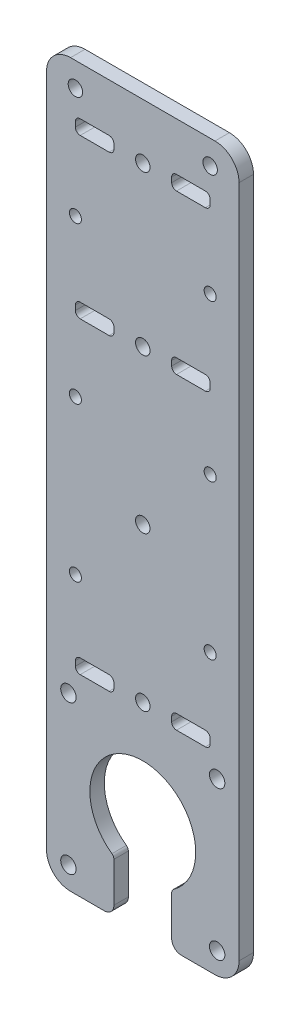
SolidWorks part; units mm, degrees
material "Acrylic (Medium-high impact)"
ref_plane "Front Plane" through (0, 0, 0) normal (0, 0, 1) x (1, 0, 0)
ref_plane "Top Plane" through (0, 0, 0) normal (0, 1, 0) x (1, 0, 0)
ref_plane "Right Plane" through (0, 0, 0) normal (1, 0, 0) x (0, 0, -1)
sketch "Sketch1" plane through (0, 0, 0) normal (0, 0, 1) x (1, 0, 0)
  line L0 (0, 75) -> (0, -75) construction
  line L1 (-20, 75) -> (20, 75)
  line L2 (-20, 75) -> (-20, -75)
  line L3 (-20, -75) -> (20, -75)
  line L4 (20, 75) -> (20, -75)
  line L5 (20, 0) -> (-20, 0) construction
  line L6 (0, -75) -> (0, -55) construction
  line L7 (0, -55) -> (6, -55) construction
  line L8 (6, -55) -> (6, -75) construction
  line L9 (0, -55) -> (-6, -55) construction
  line L10 (-6, -55) -> (-6, -75) construction
  line L11 (0, -55) -> (20, -75) construction
  line L12 (0, -55) -> (15.4503, -70.4503) construction
  line L13 (-6, -75) -> (-6, -64.2195)
  line L14 (6, -75) -> (6, -64.2195)
  line L15 (0, -75) -> (0, -35) construction
  line L16 (-20, -35) -> (20, -35) construction
  line L17 (0, -35) -> (0, -32) construction
  line L18 (-20, -32) -> (20, -32) construction
  circle A0 centre (0, -55) radius 11
  circle A1 centre (15.4503, -70.4503) radius 1.6
  circle A2 centre (-15.4503, -70.4503) radius 1.6
  circle A3 centre (-15.4503, -39.5497) radius 1.6
  circle A4 centre (15.4503, -39.5497) radius 1.6
  point P8 (0, 0)
  point P26 (0, -55)
  dimension "D1" = 4
extrude "Boss-Extrude1" add sketch "Sketch1" along normal blind 3 contours A0 L14 L3 L4 L1 L2 L13 A4 A3 A2 A1 region at (0, 5.617, 0)
fillet "Fillet1" radius 5 4 edges at (-20, -75, 1.5) (20, -75, 1.5) (-20, 75, 1.5) (20, 75, 1.5)
fillet "Fillet2" radius 2 2 edges at (6, -75, 1.5) (-6, -75, 1.5)
fillet "Fillet3" radius 1 2 edges at (6, -64.2195, 1.5) (-6, -64.2195, 1.5)
sketch "Sketch2" plane through (0, 0, 3) normal (0, 0, 1) x (1, 0, 0)
  line L0 (0, -75) -> (0, -35) construction
  line L1 (0, -35) -> (0, -33.5) construction
  line L2 (-20, -33.5) -> (20, -33.5) construction
  line L3 (-20, 70) -> (-20, -70) construction
  line L4 (20, 70) -> (20, -70) construction
  line L5 (-20, -35) -> (20, -35) construction
  line L6 (20, -35) -> (20, -32)
  line L7 (20, -32) -> (-20, -32) construction
  line L8 (-20, -32) -> (-20, -35)
  line L9 (0, 75) -> (0, 65) construction
  line L10 (-15, 75) -> (15, 75) construction
  line L11 (0, 65) -> (0, 62) construction
  line L12 (0, 62) -> (0, 32) construction
  line L13 (0, 32) -> (0, 29) construction
  line L14 (-20, 29) -> (20, 29) construction
  line L15 (20, 29) -> (20, 32) construction
  line L16 (20, 32) -> (-20, 32) construction
  line L17 (-20, 32) -> (-20, 29) construction
  line L18 (-20, 62) -> (20, 62) construction
  line L19 (20, 62) -> (20, 65) construction
  line L20 (-10, 65) -> (-10, -35) construction
  line L21 (-20, 65) -> (-20, 62) construction
  line L22 (-20, 65) -> (0, 65) construction
  line L23 (0, 65) -> (20, 65) construction
  line L24 (10, 65) -> (10, -35) construction
  line L25 (0, -33.5) -> (0, 30.5) construction
  line L26 (-10, 65) -> (-6, 65) construction
  line L27 (-10, 65) -> (-14, 65) construction
  line L28 (10, 65) -> (14, 65) construction
  line L29 (10, 65) -> (6, 65) construction
  line L30 (6, 65) -> (6, -35) construction
  line L31 (14, 65) -> (14, -35) construction
  line L32 (-14, 65) -> (-14, -35) construction
  line L33 (-6, 65) -> (-6, -35) construction
  line L34 (0, 29) -> (0, -32) construction
  line L35 (-14, 65) -> (-6, 65)
  line L36 (-14, 65) -> (-14, 62)
  line L37 (-14, 62) -> (-6, 62)
  line L38 (-6, 65) -> (-6, 62)
  line L39 (6, 65) -> (14, 65)
  line L40 (6, 65) -> (6, 62)
  line L41 (6, 62) -> (14, 62)
  line L42 (14, 65) -> (14, 62)
  line L43 (-14, 32) -> (-6, 32)
  line L44 (-14, 32) -> (-14, 29)
  line L45 (-14, 29) -> (-6, 29)
  line L46 (-6, 32) -> (-6, 29)
  line L47 (6, 32) -> (14, 32)
  line L48 (6, 32) -> (6, 29)
  line L49 (6, 29) -> (14, 29)
  line L50 (14, 32) -> (14, 29)
  line L51 (-14, -32) -> (-6, -32)
  line L52 (-14, -32) -> (-14, -35)
  line L53 (-14, -35) -> (-6, -35)
  line L54 (-6, -32) -> (-6, -35)
  line L55 (6, -32) -> (14, -32)
  line L56 (6, -32) -> (6, -35)
  line L57 (6, -35) -> (14, -35)
  line L58 (14, -32) -> (14, -35)
  circle A0 centre (0, -33.5) radius 1.5
  circle A1 centre (0, 30.5) radius 1.5
  circle A2 centre (0, 63.5) radius 1.5
  circle A3 centre (0, -1.5) radius 1.5
extrude "Cut-Extrude1" cut sketch "Sketch2" against normal blind 3 contours L54 L51 L52 L53 | L58 L55 L56 L57 | A0 | A1 | L50 L47 L48 L49 | L46 L43 L44 L45 | A2 | L38 L35 L36 L37 | L42 L39 L40 L41 | A3 region at (-10, 63.5, 3) region at (10, 63.5, 3) region at (-10, 30.5, 3) region at (10, 30.5, 3) region at (-10, -33.5, 3) region at (10, -33.5, 3) region at (0, -33.5, 3) region at (0, 30.5, 3) region at (0, 63.5, 3) region at (0, -1.5, 3)
fillet "Fillet4" radius 1 24 edges at (-6, 29, 1.5) (-14, 29, 1.5) (-6, 32, 1.5) (14, -35, 1.5) (6, -35, 1.5) (6, -32, 1.5) (14, -32, 1.5) (-6, -35, 1.5) (-14, -35, 1.5) (-14, -32, 1.5) (-6, -32, 1.5) (14, 29, 1.5) (6, 29, 1.5) (6, 32, 1.5) (14, 32, 1.5) (-14, 32, 1.5) (14, 65, 1.5) (14, 62, 1.5) (6, 65, 1.5) (6, 62, 1.5) (-14, 62, 1.5) (-6, 62, 1.5) (-6, 65, 1.5) (-14, 65, 1.5)
sketch "Sketch3" plane through (0, 0, 3) normal (0, 0, 1) x (1, 0, 0)
  line L0 (-14, 30.5) -> (-14, -1.5) construction
  line L1 (14, -1.5) -> (14, 30.5) construction
  line L2 (14, 31) -> (14, 30) construction
  line L3 (-14, 31) -> (-14, 30) construction
  line L4 (-14, -1.5) -> (-14, -33.5) construction
  line L5 (-14, -33) -> (-14, -34) construction
  line L6 (-14, -1.5) -> (14, -1.5) construction
  line L7 (14, -1.5) -> (14, -33.5) construction
  line L8 (14, -33) -> (14, -34) construction
  line L9 (-14, 30.5) -> (-14, 63.5) construction
  line L10 (-14, 64) -> (-14, 63) construction
  line L11 (14, 63.5) -> (14, 30.5) construction
  line L12 (14, 64) -> (14, 63) construction
  point P18 (-14, 47)
  point P21 (14, 47)
  point P22 (14, 14.5)
  point P23 (-14, 14.5)
  point P24 (-14, -17.5)
  point P25 (14, -17.5)
hole_wizard "Ø2.5 (2.5) Diameter Hole1" positions "Sketch7" profile "Sketch6" hole size "Ø2.5" standard "ISO"
sketch "Sketch7" plane through (0, 0, 3) normal (0, 0, 1) x (1, 0, 0)
  point P0 (14, -17.5)
  point P3 (-14, -17.5)
  point P6 (-14, 14.5)
  point P9 (14, 14.5)
  point P12 (14, 47)
  point P15 (-14, 47)
sketch "Sketch6" plane through (14, -17.5, 3) normal (1, 0, 0) x (0, -1, 0)
  line L0 (0, 0) -> (0, 6.7511)
  line L1 (0, 6.7511) -> (1.25, 6)
  line L2 (1.25, 6) -> (1.25, 0)
  line L5 (1.25, 0) -> (0, 0)
  line L10 (0, 6.7511) -> (-1.25, 6) construction
  line L11 (0, -6.35) -> (0, 107.95) construction
  dimension "Hole Dia." = 2.5
  dimension "Hole Depth" = 6
  dimension "Drill Angle" = 118
sketch "Sketch8" plane through (0, 0, 3) normal (0, 0, 1) x (1, 0, 0)
  line L0 (0, 75) -> (0, 70) construction
  line L1 (-15, 75) -> (15, 75) construction
  line L2 (0, 70) -> (-20, 70) construction
  line L3 (0, 70) -> (20, 70) construction
  line L4 (20, 70) -> (14, 70) construction
  line L5 (-20, 70) -> (-14, 70) construction
  circle A0 centre (-14, 70) radius 1.5
  circle A1 centre (14, 70) radius 1.5
extrude "Cut-Extrude2" cut sketch "Sketch8" against normal blind 10
